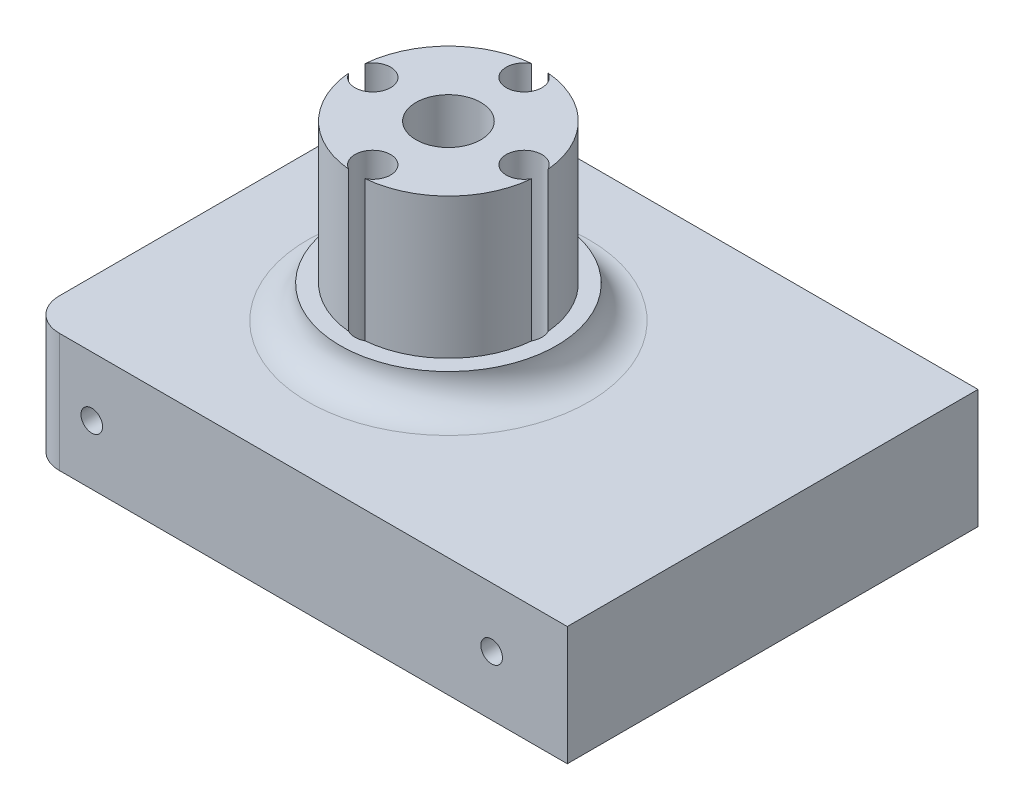
SolidWorks part; units mm, degrees
ref_plane "Спереди" through (0, 0, 0) normal (0, 0, 1) x (1, 0, 0)
ref_plane "Сверху" through (0, 0, 0) normal (0, 1, 0) x (1, 0, 0)
ref_plane "Справа" through (0, 0, 0) normal (1, 0, 0) x (0, 0, -1)
sketch "Эскиз6" plane through (0, 0, 0) normal (0, 1, 0) x (1, 0, 0)
  line L0 (-20, 0) -> (30, 0) construction
  line L1 (-20, -19) -> (30, -19)
  line L2 (-20, -19) -> (-20, 19)
  line L3 (-20, 19) -> (30, 19)
  line L4 (30, -19) -> (30, 19)
  line L5 (0, -19) -> (0, 19) construction
  dimension "D1" = 30
  dimension "D2" = 20
  dimension "D3" = 38
extrude "тело" add sketch "Эскиз6" along normal blind 11
sketch "Эскиз10" plane through (0, 11, 0) normal (0, 1, 0) x (1, 0, 0)
  circle A0 centre (0, 0) radius 10
  dimension "D1" = 20
extrude "основание оси" add sketch "Эскиз10" along normal blind 3
fillet "Скругление1" radius 3 1 edges at (0, 11, -10)
fillet "Скругление2" radius 3 2 edges at (-20, 5.5, 19) (-20, 5.5, -19)
sketch "Эскиз13" plane through (0, 0, 19) normal (0, 0, 1) x (1, 0, 0)
  line L0 (30, 5.5) -> (-17, 5.5) construction
  line L1 (30, 11) -> (30, 0) construction
  line L2 (-17, 11) -> (-17, 0) construction
  circle A0 centre (-14, 5.5) radius 1
  circle A1 centre (23, 5.5) radius 1
  dimension "D1" = 2
  dimension "D2" = 37
  dimension "D3" = 7
extrude "отверстия под шурупы" cut sketch "Эскиз13" against normal through all
sketch "Эскиз15" plane through (0, 14, 0) normal (0, 1, 0) x (1, 0, 0)
  circle A0 centre (0, 0) radius 8.5
  dimension "D1" = 17
extrude "ось" add sketch "Эскиз15" along normal blind 13
sketch "Эскиз16" plane through (0, 27, 0) normal (0, 1, 0) x (1, 0, 0)
  circle A0 centre (0, 0) radius 7 construction
  circle A1 centre (0, 7) radius 1.65
  circle A2 centre (7, 0) radius 1.65
  circle A3 centre (0, -7) radius 1.65
  circle A4 centre (-7, 0) radius 1.65
  dimension "D1" = 14
  dimension "D2" = 3.3
extrude "крепление к серве" cut sketch "Эскиз16" against normal through all
sketch "Эскиз17" plane through (0, 27, 0) normal (0, 1, 0) x (1, 0, 0)
  circle A0 centre (0, 0) radius 3
  dimension "D1" = 6
extrude "отверстие под болтик" cut sketch "Эскиз17" against normal through all
sketch "Эскиз18" plane through (0, 0, 0) normal (0, -1, 0) x (1, 0, 0)
  line L0 (-9.1213, 2.1213) -> (-2.1213, 9.1213)
  line L1 (2.1213, 9.1213) -> (9.1213, 2.1213)
  line L3 (9.1213, -2.1213) -> (2.1213, -9.1213)
  line L5 (-2.1213, -9.1213) -> (-9.1213, -2.1213)
  arc A0 (2.1213, 9.1213) -> (-2.1213, 9.1213) centre (0, 7) ccw
  arc A1 (9.1213, -2.1213) -> (9.1213, 2.1213) centre (7, 0) ccw
  arc A2 (-2.1213, -9.1213) -> (2.1213, -9.1213) centre (0, -7) ccw
  arc A3 (-9.1213, 2.1213) -> (-9.1213, -2.1213) centre (-7, 0) ccw
  dimension "D1" = 3
extrude "отверстия под шляпки" cut sketch "Эскиз18" against normal blind 6
chamfer "Фаска2" distance 1.5 angle 45 4 edges at (0, 6, -8.65) (7, 6, -1.65) (0, 6, 5.35) (-7, 6, -1.65)
